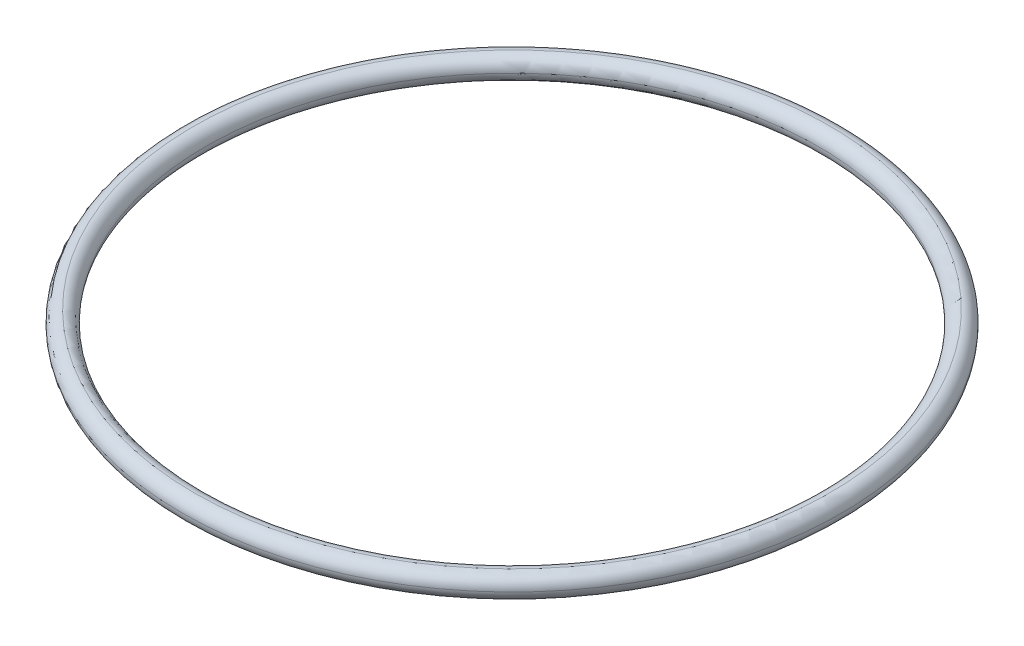
SolidWorks part; units mm, degrees
ref_plane "Plano frontal" through (0, 0, 0) normal (0, 0, 1) x (1, 0, 0)
ref_plane "Plano superior" through (0, 0, 0) normal (0, 1, 0) x (1, 0, 0)
ref_plane "Plano direito" through (0, 0, 0) normal (1, 0, 0) x (0, 0, -1)
sketch "Esboço1" plane through (0, 0, 0) normal (0, 1, 0) x (1, 0, 0)
  circle A0 centre (0, 0) radius 32.5
  circle A1 centre (0, 0) radius 35
  dimension "D1" = 65
  dimension "D2" = 2.5
extrude "Ressalto-extrusão1" add sketch "Esboço1" along normal blind 2.5
fillet "Filete3" radius 1.25 4 edges at (0, 0, 32.5) (0, 0, 35) (0, 2.5, 35) (0, 2.5, 32.5)
